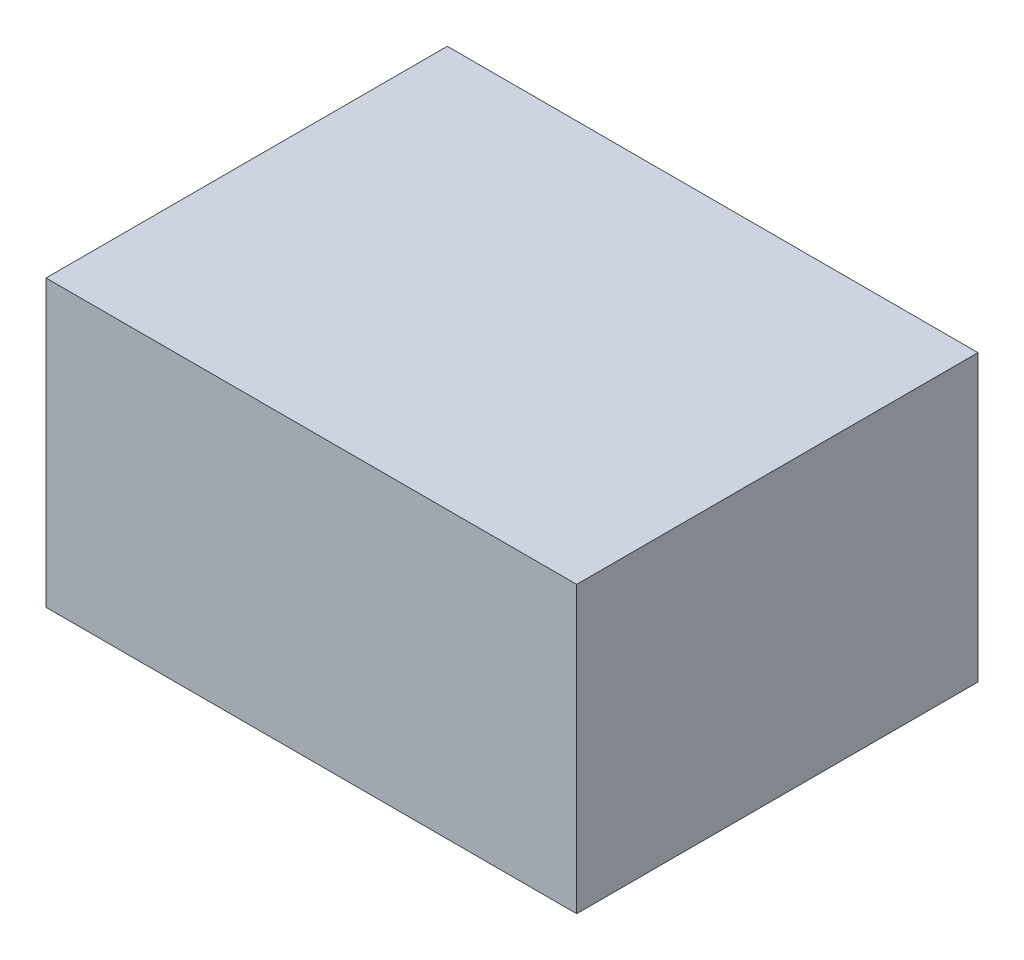
SolidWorks part; units mm, degrees
ref_plane "Front Plane" through (0, 0, 0) normal (0, 0, 1) x (1, 0, 0)
ref_plane "Top Plane" through (0, 0, 0) normal (0, 1, 0) x (1, 0, 0)
ref_plane "Right Plane" through (0, 0, 0) normal (1, 0, 0) x (0, 0, -1)
sketch "Sketch1" plane through (0, 0, 0) normal (0, 1, 0) x (1, 0, 0)
  line L1 (-160, -121) -> (160, -121)
  line L2 (-160, -121) -> (-160, 121)
  line L3 (-160, 121) -> (160, 121)
  line L4 (160, -121) -> (160, 121)
  line L5 (-160, -121) -> (160, 121) construction
  line L6 (-160, 121) -> (160, -121) construction
  point P0 (0, 0)
  dimension "D1" = 320
  dimension "D2" = 242
extrude "Boss-Extrude1" add sketch "Sketch1" along normal blind 172
equation "\"PCLength\"= 320mm'Length across I/O from PS to GPU"
equation "\"PCWidth\"= 242mm'Distance of longest part parallel to GPU(ussually GPU)"
equation "\"PCHeight\"= 172mm'Tallest point with mobo laying flat"
equation "\"WallThickness\"= 9mm'Thickness of each outer tank wall"
equation "\"ThermoBarrierThickness\"= 3mm'Thickness of barrier between hot side and cold side"
equation "\"HotSideGap\"= 25mm'Space in the hot side for a pump"
equation "\"PCClearance\"= 30mm'Clearance from top of tank to top of PC"
equation "\"RadiatorHeight\"= 275mm'Final Height from ground of radiators"
equation "\"D1@Sketch1\"=\"PCLength\""
equation "\"D2@Sketch1\"=\"PCWidth\""
equation "\"D1@Boss-Extrude1\"=\"PCHeight\""
